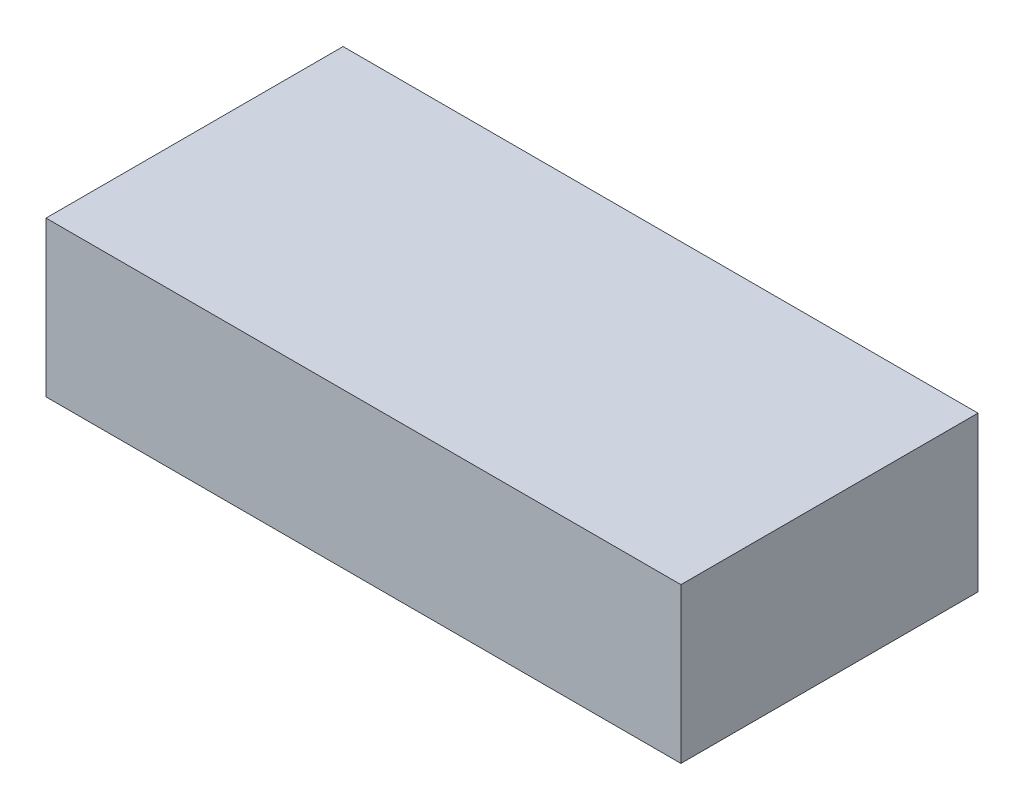
SolidWorks part; units mm, degrees
ref_plane "Front Plane" through (0, 0, 0) normal (0, 0, 1) x (1, 0, 0)
ref_plane "Top Plane" through (0, 0, 0) normal (0, 1, 0) x (1, 0, 0)
ref_plane "Right Plane" through (0, 0, 0) normal (1, 0, 0) x (0, 0, -1)
sketch "Sketch1" plane through (0, 0, 0) normal (0, 1, 0) x (1, 0, 0)
  line L1 (44.69, -20.91) -> (-44.69, -20.91)
  line L2 (44.69, -20.91) -> (44.69, 20.91)
  line L3 (44.69, 20.91) -> (-44.69, 20.91)
  line L4 (-44.69, -20.91) -> (-44.69, 20.91)
  line L5 (44.69, -20.91) -> (-44.69, 20.91) construction
  line L6 (44.69, 20.91) -> (-44.69, -20.91) construction
  circle A0 centre (-25.39, 11.93) radius 2.2
  circle A1 centre (-25.39, -11.93) radius 2.2
  circle A2 centre (14.65, 11.93) radius 2.2
  circle A3 centre (14.65, -11.93) radius 2.2
  point P0 (0, 0)
  dimension "D4" = 4.4
  dimension "D1" = 41.82
  dimension "D2" = 89.38
  dimension "D3" = 8.98
  dimension "D5" = 19.3
  dimension "D7" = 19.3
  dimension "D8" = 8.98
  dimension "D10" = 30.04
  dimension "D9" = 8.98
  dimension "D6" = 8.98
  dimension "D11" = 30.04
extrude "Boss-Extrude6" add sketch "Sketch1" along normal blind 21.8 contours L2 L1 L4 L3
extrude "Cut-Extrude2" cut sketch "Sketch1<13>" along normal blind 10 contours A0 | A2 | A3 | A1
sketch "Sketch1<13>" plane through (0, 0, 0) normal (0, 1, 0) x (1, 0, 0) same geometry as "Sketch1"
equation "\"D3@Sketch1\"=6.78+\"D4@Sketch1\"/2"
equation "\"D5@Sketch1\"=17.1+\"D4@Sketch1\"/2"
equation "\"D7@Sketch1\"=\"D5@Sketch1\""
equation "\"D8@Sketch1\"=\"D3@Sketch1\""
equation "\"D10@Sketch1\"=27.84+\"D4@Sketch1\"/2"
equation "\"D9@Sketch1\"=\"D8@Sketch1\""
equation "\"D6@Sketch1\"=\"D3@Sketch1\""
equation "\"D11@Sketch1\"=\"D10@Sketch1\""
